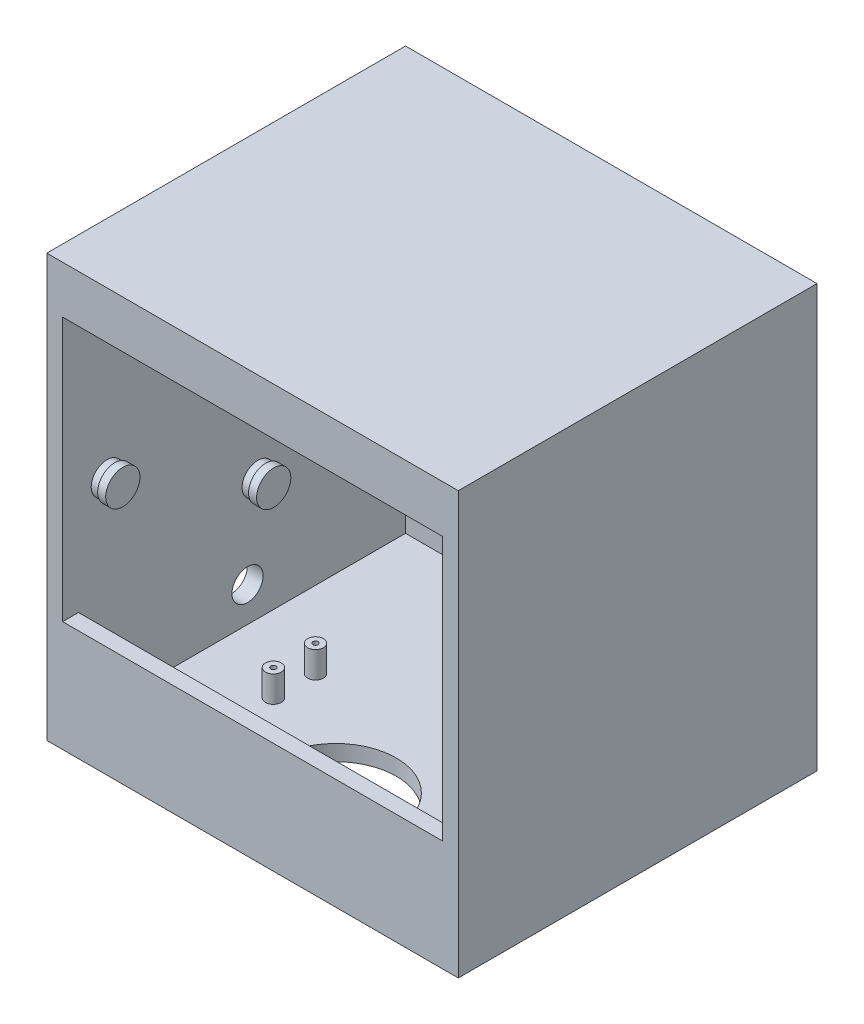
SolidWorks part; units mm, degrees
ref_plane "Front Plane" through (0, 0, 0) normal (0, 0, 1) x (1, 0, 0)
ref_plane "Top Plane" through (0, 0, 0) normal (0, 1, 0) x (1, 0, 0)
ref_plane "Right Plane" through (0, 0, 0) normal (1, 0, 0) x (0, 0, -1)
sketch "Base Plate Sketch" plane through (0, 0, 0) normal (0, 1, 0) x (1, 0, 0)
  line L1 (-176.9042, 232.645) -> (280.2958, 232.645)
  line L2 (-176.9042, 232.645) -> (-176.9042, -161.055)
  line L3 (-176.9042, -161.055) -> (280.2958, -161.055)
  line L4 (280.2958, 232.645) -> (280.2958, -161.055)
  line L5 (-195.9542, 251.695) -> (299.3458, 251.695)
  line L6 (-195.9542, 251.695) -> (-195.9542, -180.105)
  line L7 (-195.9542, -180.105) -> (299.3458, -180.105)
  line L8 (299.3458, 251.695) -> (299.3458, -180.105)
  line L9 (51.6958, 232.645) -> (51.6958, -161.055)
  circle A0 centre (51.6958, -80.0925) radius 73.025
  circle A1 centre (-72.1292, -82.0299) radius 4.1
  circle A2 centre (-72.1292, 203.67) radius 4.7625
  circle A3 centre (-84.8292, 32.22) radius 9.5
  circle A4 centre (-84.8292, -18.5299) radius 9.5
  circle A5 centre (-84.8292, 32.22) radius 3.175
  circle A6 centre (-84.8292, -18.5299) radius 3.175
  circle A7 centre (175.5208, -82.0299) radius 4.1
  circle A8 centre (188.2208, -18.5299) radius 3.175
  circle A9 centre (188.2208, -18.5299) radius 9.5
  circle A10 centre (188.2208, 32.22) radius 3.175
  circle A11 centre (188.2208, 32.22) radius 9.5
  circle A12 centre (175.5208, 203.67) radius 4.7625
  dimension "D7" = 146.05
  dimension "D9" = 8.2
  dimension "D10" = 12.7
  dimension "D11" = 63.5
  dimension "D12" = 9.525
  dimension "D13" = 12.7
  dimension "D14" = 19
  dimension "D15" = 19
  dimension "D19" = 6.35
  dimension "D20" = 6.35
  dimension "D1" = 393.7
  dimension "D2" = 457.2
  dimension "D3" = 19.05
  dimension "D4" = 19.05
  dimension "D5" = 19.05
  dimension "D6" = 19.05
  dimension "D8" = 312.7375
  dimension "D16" = 50.75
  dimension "D17" = 123.825
  dimension "D21" = 28.975
  dimension "D22" = 171.45
extrude "Boss-Extrude2" add sketch "Base Plate Sketch" along normal blind 31.75 contours A10 | A11 | A8 | A9 | A5 | A3 | A6 | A4
extrude "Boss-Extrude3" add sketch "Sketch1<5>" against normal blind 19.05 contours L5 L8 L7 L6
sketch "Sketch1<5>" plane through (0, 0, 0) normal (0, 1, 0) x (1, 0, 0) same geometry as "Base Plate Sketch"
extrude "Cut-Extrude1" cut sketch "Sketch1<6>" against normal blind 99.05 contours A2 | A1 | A0 | A7 | A12
sketch "Sketch1<6>" plane through (0, 0, 0) normal (0, 1, 0) x (1, 0, 0) same geometry as "Base Plate Sketch"
extrude "Boss-Extrude4" add sketch "Sketch1<7>" along normal blind 469.9 contours L6 L7 L8 L5 | L2 L3 L4 L1
sketch "Sketch1<7>" plane through (0, 0, 0) normal (0, 1, 0) x (1, 0, 0) same geometry as "Base Plate Sketch"
ref_plane "Plane1" through (-176.9042, 0, -232.645) normal (1, 0, 0) x (0, 0, -1)
sketch "Back Wall Sketch" plane through (0, 0, -232.645) normal (0, 0, 1) x (1, 0, 0)
  line L0 (-176.9042, 114.3) -> (280.2958, 114.3)
  line L1 (-176.9042, 469.9) -> (-176.9042, 0) construction
  line L2 (280.2958, 469.9) -> (280.2958, 0) construction
  line L3 (-176.9042, 266.7) -> (280.2958, 266.7)
  line L4 (-176.9042, 0) -> (280.2958, 0) construction
  line L5 (-176.9042, 469.9) -> (280.2958, 469.9) construction
  line L6 (51.6958, 266.7) -> (51.6958, 469.9)
  line L7 (280.2958, 266.7) -> (280.2958, 114.3)
  line L8 (-176.9042, 266.7) -> (-176.9042, 114.3)
  circle A0 centre (-117.9716, 342.325) radius 1.875
  circle A2 centre (-21.0417, 294.9875) radius 1.875
  circle A4 centre (-117.9716, 316.575) radius 1.875
  circle A5 centre (124.4333, 294.9875) radius 1.875
  circle A6 centre (221.3633, 342.325) radius 1.875
  circle A7 centre (221.3633, 316.575) radius 1.875
  circle A8 centre (184.1213, 148.3) radius 16.8
  dimension "D3" = 3.75
  dimension "D4" = 3.75
  dimension "D5" = 3.75
  dimension "D10" = 33.6
  dimension "D1" = 114.3
  dimension "D2" = 152.4
  dimension "D6" = 127.575
  dimension "D7" = 25.75
  dimension "D8" = 174.9125
  dimension "D9" = 155.8625
  dimension "D11" = 96.1746
  dimension "D12" = 118.4
extrude "Boss-Extrude5" add sketch "Back Wall Sketch" against normal blind 38.3 contours L8 L0 L7 L3
extrude "Cut-Extrude2" cut sketch "Back Wall Sketch<5>" against normal blind 19.25 contours L3 L7 L0 L8
sketch "Back Wall Sketch<5>" plane through (0, 0, -232.645) normal (0, 0, 1) x (1, 0, 0) same geometry as "Back Wall Sketch"
extrude "Cut-Extrude5" cut sketch "Back Wall Sketch<7>" against normal blind 28.875 contours A8
sketch "Back Wall Sketch<7>" plane through (0, 0, -232.645) normal (0, 0, 1) x (1, 0, 0) same geometry as "Back Wall Sketch"
extrude "Cut-Extrude6" cut sketch "Back Wall Sketch<8>" against normal blind 28.875 contours A2 | A4 | A0 | A6 | A7 | A5
sketch "Back Wall Sketch<8>" plane through (0, 0, -232.645) normal (0, 0, 1) x (1, 0, 0) same geometry as "Back Wall Sketch"
sketch "Left Wall Sketch" plane through (-176.9042, 0, 0) normal (1, 0, 0) x (0, 0, -1)
  line L0 (232.645, 0) -> (-161.055, 0) construction
  line L1 (251.695, 266.7) -> (251.695, 114.3) construction
  line L2 (232.645, 114.3) -> (232.645, 0) construction
  circle A0 centre (-126.7142, 237.44) radius 19
  circle A1 centre (54.8951, 146) radius 19
  circle A2 centre (42.445, 41.61) radius 18.75
  dimension "D1" = 38
  dimension "D2" = 38
  dimension "D3" = 37.5
  dimension "D5" = 146
  dimension "D9" = 41.61
  dimension "D4" = 237.44
  dimension "D6" = 378.4092
  dimension "D7" = 196.8
  dimension "D8" = 190.2
extrude "Cut-Extrude7" cut sketch "Left Wall Sketch" against normal blind 28.875 contours A2
extrude "Boss-Extrude6" add sketch "Left Wall Sketch<3>" along normal blind 9.35 contours A1 | A0
sketch "Left Wall Sketch<3>" plane through (-176.9042, 0, 0) normal (1, 0, 0) x (0, 0, -1) same geometry as "Left Wall Sketch"
sketch "Sketch5" plane through (-167.5542, 0, 0) normal (1, 0, 0) x (0, 0, -1)
  circle A0 centre (-126.7142, 237.44) radius 20.6
  circle A1 centre (54.8951, 146) radius 20.6
  dimension "D1" = 41.2
  dimension "D2" = 41.2
extrude "Boss-Extrude7" add sketch "Sketch5" along normal blind 9.7
sketch "Chamber Door Sketch" plane through (0, 0, 161.055) normal (0, 0, -1) x (-1, 0, 0)
  line L0 (-280.2958, 431.8) -> (176.9042, 431.8)
  line L1 (-280.2958, 469.9) -> (-280.2958, 0) construction
  line L2 (176.9042, 469.9) -> (176.9042, 0) construction
  line L3 (-280.2958, 114.3) -> (176.9042, 114.3)
  line L4 (176.9042, 0) -> (-280.2958, 0) construction
  line L5 (176.9042, 469.9) -> (-280.2958, 469.9) construction
  line L6 (-280.2958, 431.8) -> (-280.2958, 114.3)
  line L7 (176.9042, 431.8) -> (176.9042, 114.3)
  dimension "D1" = 114.3
  dimension "D2" = 38.1
extrude "Cut-Extrude8" cut sketch "Chamber Door Sketch" against normal blind 25.4 contours L0 L7 L3 L6
sketch "Top Sketch" plane through (0, 469.9, 0) normal (0, 1, 0) x (1, 0, 0)
  line L1 (-195.9542, 251.695) -> (299.3458, 251.695)
  line L2 (-195.9542, 251.695) -> (-195.9542, -180.105)
  line L3 (-195.9542, -180.105) -> (299.3458, -180.105)
  line L4 (299.3458, 251.695) -> (299.3458, -180.105)
extrude "Boss-Extrude8" add sketch "Top Sketch" along normal blind 19.05 contours L4 L3 L2 L1
sketch "Sketch7" plane through (0, 469.9, 0) normal (0, -1, 0) x (1, 0, 0)
  line L0 (-176.9042, -232.645) -> (280.2958, -232.645) construction
  line L1 (22.0201, -181.825) -> (11.0101, -162.755)
  line L2 (11.0101, -162.755) -> (-11.0101, -162.755)
  line L3 (-11.0101, -162.755) -> (-22.0201, -181.825)
  line L4 (-22.0201, -181.825) -> (-11.0101, -200.895)
  line L5 (-11.0101, -200.895) -> (11.0101, -200.895)
  line L6 (11.0101, -200.895) -> (22.0201, -181.825)
  circle A0 centre (0, -181.825) radius 19.07 construction
  point P1 (0, -200.895)
  dimension "D1" = 38.14
  dimension "D2" = 31.75
extrude "Boss-Extrude9" add sketch "Sketch7" along normal blind 12.7 contours L2 L3 L4 L5 L6 L1
